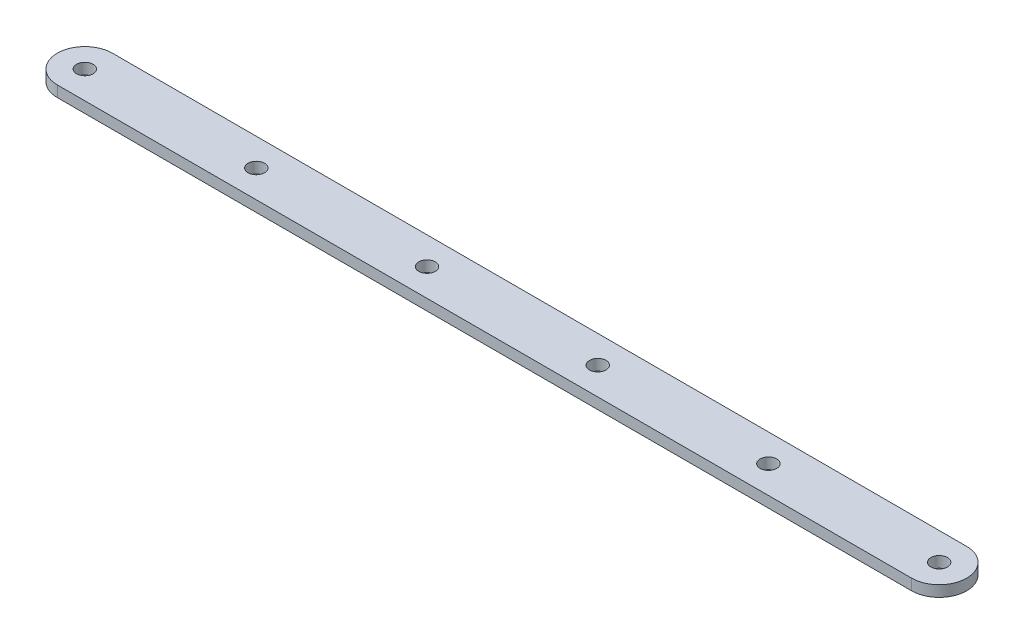
SolidWorks part; units mm, degrees
ref_plane "Front Plane" through (0, 0, 0) normal (0, 0, 1) x (1, 0, 0)
ref_plane "Top Plane" through (0, 0, 0) normal (0, 1, 0) x (1, 0, 0)
ref_plane "Right Plane" through (0, 0, 0) normal (1, 0, 0) x (0, 0, -1)
sketch "Sketch1" plane through (0, 0, 0) normal (0, 1, 0) x (1, 0, 0)
  line L0 (-186.4, 0) -> (124.05, 0) construction
  line L1 (-186.4, 0) -> (124.05, 0) construction
  line L2 (-186.4, 10) -> (124.05, 10)
  line L3 (-186.4, -10) -> (124.05, -10)
  arc A0 (-186.4, 10) -> (-186.4, -10) centre (-186.4, 0) ccw
  arc A1 (124.05, -10) -> (124.05, 10) centre (124.05, 0) ccw
  circle A2 centre (-186.4, 0) radius 3.01
  circle A3 centre (-124.1, 0) radius 3.01
  circle A4 centre (-62.05, 0) radius 3.01
  circle A5 centre (0, 0) radius 3.01
  circle A6 centre (62, 0) radius 3.01
  circle A7 centre (124.05, 0) radius 3.01
  point P3 (-124.1, 0)
  point P4 (-62.05, 0)
  point P5 (62, 0)
  point P6 (-31.175, 0)
  dimension "D6" = 20
  dimension "D7" = 6.02
  dimension "D1" = 62.3
  dimension "D2" = 62.05
  dimension "D3" = 62.05
  dimension "D4" = 62
  dimension "D5" = 62.05
extrude "Boss-Extrude1" add sketch "Sketch1" along normal blind 4
